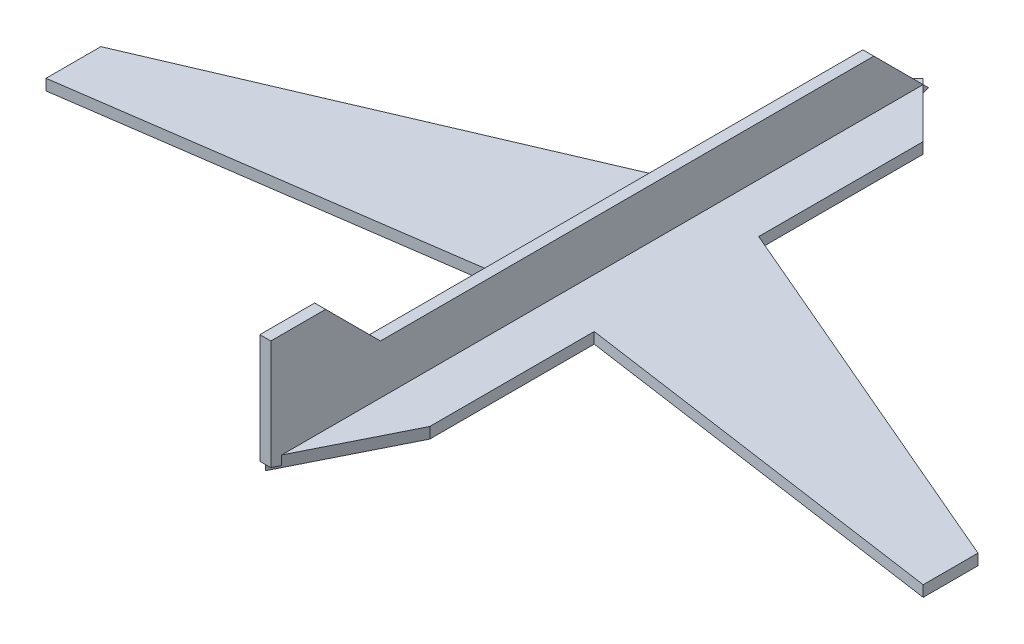
SolidWorks part; units mm, degrees
ref_plane "Front Plane" through (0, 0, 0) normal (0, 0, 1) x (1, 0, 0)
ref_plane "Top Plane" through (0, 0, 0) normal (0, 1, 0) x (1, 0, 0)
ref_plane "Right Plane" through (0, 0, 0) normal (1, 0, 0) x (0, 0, -1)
sketch "Sketch1" plane through (0, 0, 0) normal (0, 1, 0) x (1, 0, 0)
  line L0 (0, 5) -> (0, -7)
  line L7 (1, 4) -> (1, 1)
  line L8 (0, 5) -> (1, 4)
  line L9 (-8, -2) -> (-8, -3)
  line L10 (0, 0) -> (0, 1)
  line L11 (1, -2) -> (1, -5)
  line L14 (0, -7) -> (1, -5)
  line L15 (0, -7) -> (-1, -5)
  line L16 (0, 0) -> (0, 0)
  line L19 (1, 1) -> (8, -2)
  line L20 (8, -2) -> (8, -3)
  line L21 (8, -3) -> (1, -2)
  line L22 (-1, -2) -> (-1, -5)
  line L23 (-8, -3) -> (-1, -2)
  line L24 (0, 5) -> (-1, 4)
  line L25 (-1, 4) -> (-1, 1)
  line L26 (-1, 1) -> (-8, -2)
  line L27 (1, 1) -> (1, -2)
  line L28 (-1, -2) -> (-1, 1)
sketch "Sketch2" plane through (0, 0, 0) normal (1, 0, 0) x (0, 0, -1)
  line L0 (5, 0) -> (4, 1)
  line L1 (4.021, 0) -> (5.0104, 0) construction
  line L2 (4, 1) -> (-5, 1)
  line L6 (2, -1) -> (5, 0)
  line L7 (2, -1) -> (-4, -1)
  line L8 (-4, -1) -> (-7, 0)
  line L9 (-4.979, 0) -> (-6.9896, 0) construction
  line L10 (-7, 0) -> (-7, 2)
  line L11 (-7, 2) -> (-6, 2)
  line L12 (-6, 2) -> (-5, 1)
  point P6 (0, 0)
  point P7 (0, 0)
  point P8 (0, 0)
  point P15 (0, 0)
  point P16 (0, 0)
  point P17 (0, 0)
  point P18 (0, 0)
  point P19 (0, 0)
  point P20 (0, 0)
  point P21 (0, 0)
  point P22 (0, 0)
  point P23 (0, 0)
extrude "Boss-Extrude1" add sketch "Sketch1" along normal blind 0.1 and the other way blind 0.1 contours L21 L20 L19 L7 L8 L0 L14 L11 | L25 L26 L9 L23 L22 L15 L0 L24 | L19 L27 L21 L20 | L23 L28 L26 L9 region at (0.4762, 0, 0.7619) region at (-0.4762, 0, 0.7619) region at (3.9167, 0, 1.3333) region at (-3.9167, 0, 1.3333)
extrude "Boss-Extrude2" add sketch "Sketch2" along normal blind 0.1 and the other way blind 0.1
